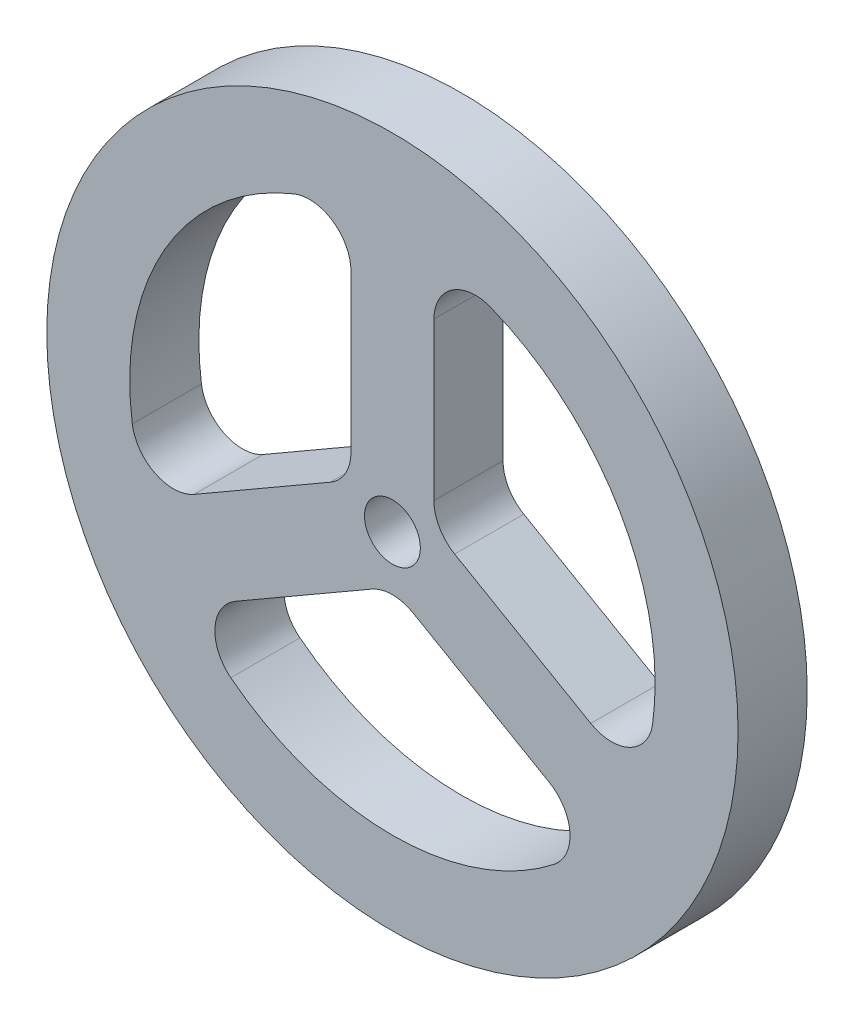
SolidWorks part; units mm, degrees
material "ABS"
ref_plane "Front Plane" through (0, 0, 0) normal (0, 0, 1) x (1, 0, 0)
ref_plane "Top Plane" through (0, 0, 0) normal (0, 1, 0) x (1, 0, 0)
ref_plane "Right Plane" through (0, 0, 0) normal (1, 0, 0) x (0, 0, -1)
sketch "Sketch1" plane through (0, 0, 0) normal (0, 0, 1) x (1, 0, 0)
  line L0 (0, 0) -> (0, 24.13) construction
  line L1 (0, 0) -> (20.8972, -12.065) construction
  line L2 (0, 0) -> (-20.8972, -12.065) construction
  line L3 (-3.81, 2.1997) -> (-22.8022, -8.7654)
  line L4 (0, -4.3994) -> (18.9922, -15.3646)
  line L5 (3.81, 2.1997) -> (3.81, 24.13)
  line L6 (0, -4.3994) -> (-18.9922, -15.3646)
  line L7 (3.81, 2.1997) -> (22.8022, -8.7654)
  line L8 (-3.81, 2.1997) -> (-3.81, 24.13)
  line L9 (1.905, 3.2996) -> (22.8022, -8.7654) construction
  line L10 (3.81, 0) -> (3.81, 24.13) construction
  line L11 (-1.905, 3.2996) -> (-22.8022, -8.7654) construction
  line L12 (-3.81, 0) -> (-3.81, 24.13) construction
  line L13 (-1.905, -3.2996) -> (18.9922, -15.3646) construction
  line L14 (1.905, -3.2996) -> (-18.9922, -15.3646) construction
  circle A0 centre (0, 0) radius 31.75
  circle A1 centre (0, 0) radius 2.5654
  arc A3 (-18.7301, -15.2132) -> (18.7301, -15.2132) centre (0, 0) ccw
  arc A4 (22.5401, -8.6141) -> (3.81, 23.8273) centre (0, 0) ccw
  arc A5 (-3.81, 23.8273) -> (-22.5401, -8.6141) centre (0, 0) ccw
  point P12 (0, 0)
  dimension "D1" = 63.5
  dimension "D2" = 5.1308
  dimension "D3" = 7.62
  dimension "D5" = 3.81
  dimension "D6" = 3.81
  dimension "D4" = 3
extrude "Boss-Extrude3" add sketch "Sketch1" along normal blind 6.35 contours A0 A5 L8 L3 A4 L7 L5 A3 L6 L4 A1 region at (-30.852, 0, 0)
fillet "Fillet1" radius 3.81 9 edges at (0, -4.3994, 3.175) (-18.7301, -15.2132, 3.175) (3.81, 23.8273, 3.175) (3.81, 2.1997, 3.175) (-22.5401, -8.6141, 3.175) (-3.81, 2.1997, 3.175) (-3.81, 23.8273, 3.175) (18.7301, -15.2132, 3.175) (22.5401, -8.6141, 3.175)
equation "\"rodThick\"= 0.085in"
equation "\"clear\"= 0.003in"
